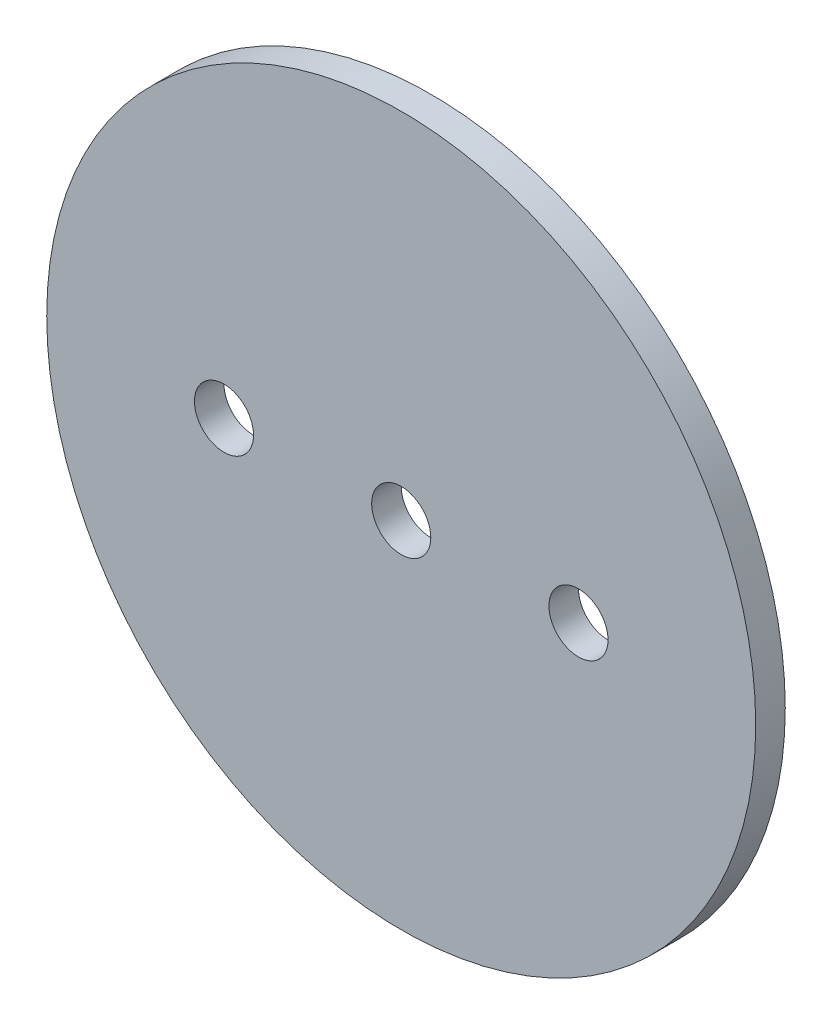
SolidWorks part; units mm, degrees
ref_plane "Front Plane" through (0, 0, 0) normal (0, 0, 1) x (1, 0, 0)
ref_plane "Top Plane" through (0, 0, 0) normal (0, 1, 0) x (1, 0, 0)
ref_plane "Right Plane" through (0, 0, 0) normal (1, 0, 0) x (0, 0, -1)
sketch "Sketch1" plane through (0, 0, 0) normal (0, 0, 1) x (1, 0, 0)
  circle A0 centre (0, 0) radius 38.1
extrude "Boss-Extrude1" add sketch "Sketch1" along normal mid plane 3.175
sketch "Sketch2" plane through (0, 0, 1.5875) normal (0, 0, 1) x (1, 0, 0)
  line L0 (-1000, 0) -> (49000, 0) construction
  point P1 (0, 0)
  point P4 (19.05, 0)
  point P5 (-19.05, 0)
  dimension "D1" = 19.05
  dimension "D2" = 38.1
hole_wizard "1/4 (0.25) Diameter Hole1" positions "Sketch2" profile "Sketch3" hole size "1/4" standard "ANSI Inch" end condition through all
sketch "Sketch3" plane through (-19.05, 0, 1.5875) normal (1, 0, 0) x (0, -1, 0)
  line L0 (0, 0) -> (0, 3.175)
  line L1 (0, 3.175) -> (3.175, 3.175)
  line L2 (3.175, 3.175) -> (3.175, 0)
  line L5 (3.175, 0) -> (0, 0)
  line L11 (0, -6.35) -> (0, 107.95) construction
  dimension "Thru Hole Dia." = 6.35
  dimension "Thru Hole Depth" = 3.175
equation "\"AIRFRAME_OD\"= 3.091in"
equation "\"AIRFRAME_ID\"= 3.00in"
equation "\"FLAT_T\" = 0.125in"
equation "\"NOSE_EXP_L\"= 3.5in"
equation "\"NOSE_SHOULDER_L\" = 5in"
equation "\"MAIN_L\" = 30in"
equation "\"RECO_COUP_L\" = 6in"
equation "\"RECO_SWITCH_L\" = 1.5in"
equation "\"DROGUE_L\" = 14in"
equation "\"ATS_FORE_COUP_L\" = 4in"
equation "\"ATS_AFT_COUP_L\" = 4in"
equation "\"LOWER_L\" = 16in"
equation "\"FIN_N\" = 4"
equation "\"CR_AFT_X\" = 0.5in"
equation "\"CR_FORE_X\" = 6in"
equation "\"FIN_ROOT\" = 5in"
equation "\"FIN_X\" = 0.75in"
equation "\"MOTOR_OD\" = 2.25in"
equation "\"MOTOR_ID\" = 2.126in"
equation "\"COUPLER_OD\" = 2.998in"
equation "\"COUPLER_ID\" = 2.875in"
equation "\"D1@Sketch1\"=\"AIRFRAME_ID\""
equation "\"D1@Boss-Extrude1\"=\"FLAT_T\""
equation "\"RECO_ROD_X\" = 1.5in"
equation "\"ATS_ROD_X\" = 2in"
equation "\"D1@Sketch2\"=\"RECO_ROD_X\"*0.5"
equation "\"D2@Sketch2\"=\"RECO_ROD_X\""
